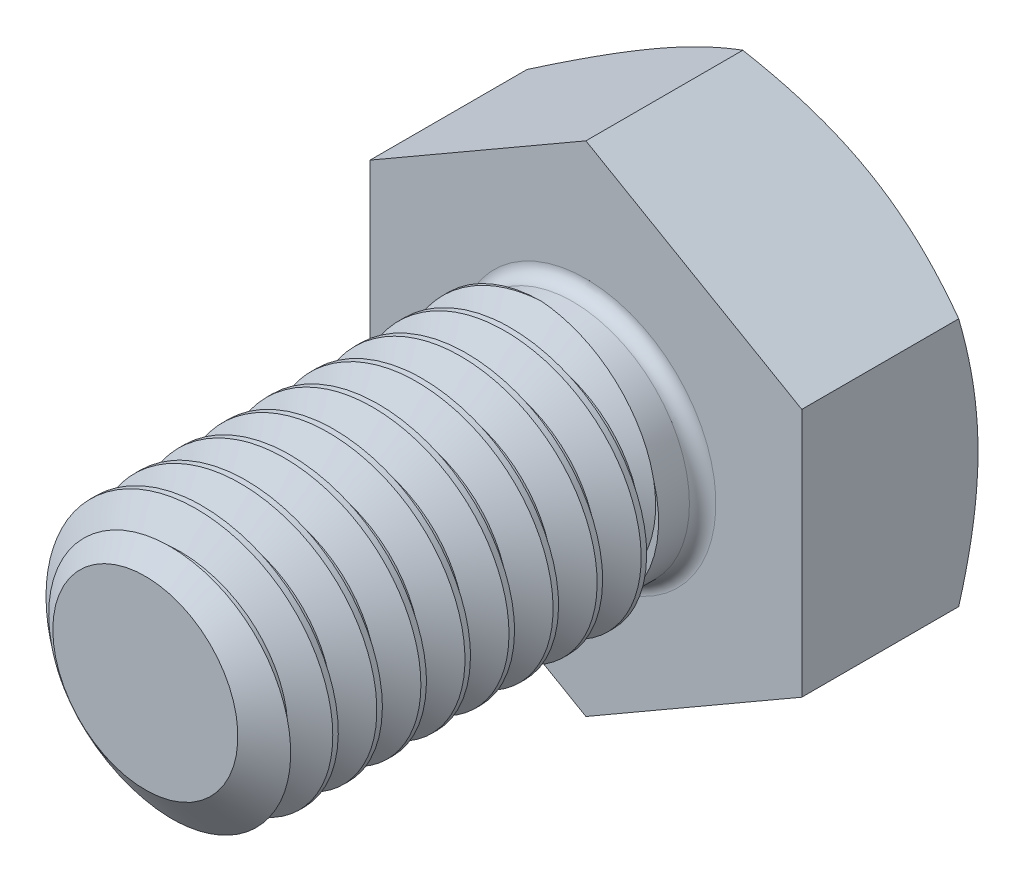
SolidWorks part; units mm, degrees
material "AISI 1020"
ref_plane "Front Plane" through (0, 0, 0) normal (0, 0, 1) x (1, 0, 0)
ref_plane "Top Plane" through (0, 0, 0) normal (0, 1, 0) x (1, 0, 0)
ref_plane "Right Plane" through (0, 0, 0) normal (1, 0, 0) x (0, 0, -1)
sketch "Sketch1" plane through (0, 0, 0) normal (0, 0, 1) x (1, 0, 0)
  circle A0 centre (0, 0) radius 3
  dimension "D1" = 6
extrude "Boss-Extrude1" add sketch "Sketch1" against normal blind 10
sketch "Sketch2" plane through (0, 0, 0) normal (0, 0, 1) x (1, 0, 0)
  circle A1 centre (0, 0) radius 3
  circle A2 centre (0, 0) radius 3
  dimension "D1" = 0
curve "Helix/Spiral1" pitch 1 height 52 turns 52
sketch "Sketch3" plane through (0, 0, 0) normal (1, 0, 0) x (0, 0, -1)
  line L0 (-0.875, 3) -> (0, 3)
  line L1 (0, 3) -> (-0.375, 2.3505)
  line L2 (-0.375, 2.3505) -> (-0.5, 2.3505)
  line L3 (-0.5, 2.3505) -> (-0.875, 3)
  line L4 (-0.4375, 3) -> (-0.4375, 2.3505) construction
  line L5 (-0.6875, 2.6752) -> (-0.1875, 2.6752) construction
  dimension "D1" = 60
  dimension "D2" = 0.125
  dimension "D3" = 0.5
sweep "Cut-Sweep1" cut profiles "Sketch3" path "Helix/Spiral1"
sketch "Sketch4" plane through (0, 0, 0) normal (1, 0, 0) x (0, 0, -1)
  line L0 (0, 3) -> (0.6302, 3)
  line L1 (0.6302, 3) -> (0, 2.1)
  line L2 (0, 2.1) -> (0, 3)
  line L3 (0, 3) -> (0, -1.6771) construction
  dimension "D1" = 55
  dimension "D2" = 0.9
  dimension "D3" = 3
revolve "Cut-Revolve1" cut sketch "Sketch4" angle 360 about axis through (0, 0, -10) along (0, 0, 1)
sketch "Sketch5" plane through (0, 0, -10) normal (0, 0, -1) x (-1, 0, 0)
  line L1 (4.9, -2.829) -> (4.9, 2.829)
  line L2 (4.9, 2.829) -> (0, 5.658)
  line L3 (0, 5.658) -> (-4.9, 2.829)
  line L4 (-4.9, 2.829) -> (-4.9, -2.829)
  line L5 (-4.9, -2.829) -> (0, -5.658)
  line L6 (0, -5.658) -> (4.9, -2.829)
  circle A0 centre (0, 0) radius 4.9 construction
  dimension "D1" = 9.8
extrude "Boss-Extrude2" add sketch "Sketch5" along normal blind 4
sketch "Sketch6" plane through (0, 0, -14) normal (0, 0, -1) x (-1, 0, 0)
  circle A0 centre (0, 0) radius 4.9
extrude "Cut-Extrude1" cut sketch "Sketch6" against normal blind 1 draft 60 flip side to cut
sketch "Sketch7" plane through (0, 0, 0) normal (1, 0, 0) x (0, 0, -1)
  line L0 (10, 5.658) -> (10, 2.829) construction
  line L1 (10, 3) -> (9, 3)
  line L2 (10, 3) -> (10, 0)
  line L3 (10, 0) -> (9, 0)
  line L4 (9, 3) -> (9, 0)
  dimension "D1" = 1
  dimension "D2" = 3
revolve "Revolve1" add sketch "Sketch7" angle 360 about L3
sketch "Sketch8" plane through (0, 0, 0) normal (1, 0, 0) x (0, 0, -1)
  line L0 (10, 3) -> (10, -3) construction
  line L1 (9, 3) -> (10, 3)
  line L2 (9, 3) -> (9, 2.65)
  line L3 (9, 2.65) -> (10, 2.65)
  line L4 (10, 3) -> (10, 2.65)
  dimension "D1" = 2.65
revolve "Cut-Revolve2" cut sketch "Sketch8" angle 360 about axis through (0, 0, -10) along (0, 0, 1)
fillet "Fillet1" radius 0.3 1 edges at (-2.65, 0, -10)
equation "\"M6 PITCH\"= 1.0mm"
equation "\"D2@Sketch3\"=\"M6 PITCH\"*.125"
equation "\"D3@Sketch3\"=\"M6 PITCH\"*.5"
